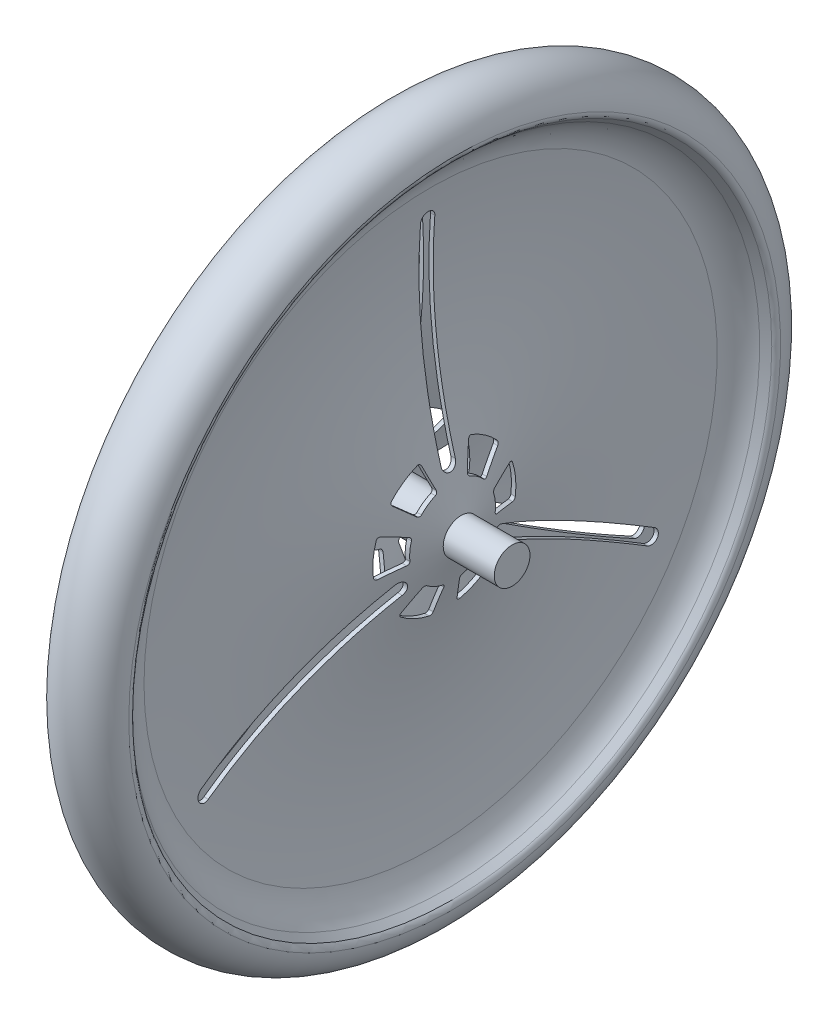
SolidWorks part; units mm, degrees
ref_plane "Front Plane" through (0, 0, 0) normal (0, 0, 1) x (1, 0, 0)
ref_plane "Top Plane" through (0, 0, 0) normal (0, 1, 0) x (1, 0, 0)
ref_plane "Right Plane" through (0, 0, 0) normal (1, 0, 0) x (0, 0, -1)
sketch "Sketch1" plane through (0, 0, 0) normal (0, 0, 1) x (1, 0, 0)
  line L0 (0, 0) -> (351.6274, 0) construction
  line L1 (0, 0) -> (0, 280.0063) construction
  line L2 (23.0895, 223.3969) -> (18.4882, 219.536)
  line L5 (-23.0895, 223.3969) -> (-18.4882, 219.536)
  line L6 (-29.3537, 12.5) -> (29.3537, 12.5)
  arc A0 (-24.8445, 227.784) -> (24.8445, 227.784) centre (0, 225) cw
  arc A1 (8.0072, 200.3052) -> (29.3537, 12.5) centre (404.869, 150.2979) ccw
  arc A2 (18.4882, 219.536) -> (8.0072, 200.3052) centre (37.7718, 196.5546) ccw
  arc A3 (24.8445, 227.784) -> (23.0895, 223.3969) centre (19.8756, 227.2272) cw
  arc A4 (-8.0072, 200.3052) -> (-29.3537, 12.5) centre (-404.869, 150.2979) cw
  arc A5 (-18.4882, 219.536) -> (-8.0072, 200.3052) centre (-37.7718, 196.5546) cw
  arc A6 (-24.8445, 227.784) -> (-23.0895, 223.3969) centre (-19.8756, 227.2272) ccw
  point P2 (0, 250)
  point P27 (9.6791, 212.1442)
  point P31 (25, 225)
  dimension "D2" = 25
  dimension "D6" = 400
  dimension "D7" = 30
  dimension "D8" = 5
  dimension "D1" = 25
  dimension "D3" = 250
  dimension "D4" = 50
  dimension "D5" = 20
revolve "Revolve1" add sketch "Sketch1" angle 360 about L0
shell "Shell2" thickness 3
sketch "Sketch2" plane through (0, 0, 0) normal (1, 0, 0) x (0, 0, -1)
  line L0 (0, 40) -> (0, 180) construction
  line L1 (-5, 40) -> (-5, 180)
  line L2 (5, 40) -> (5, 180)
  line L3 (32.141, -24.3301) -> (153.3846, -94.3301)
  line L4 (37.141, -15.6699) -> (158.3846, -85.6699)
  line L5 (34.641, -20) -> (155.8846, -90) construction
  line L6 (-37.141, -15.6699) -> (-158.3846, -85.6699)
  line L7 (-32.141, -24.3301) -> (-153.3846, -94.3301)
  line L8 (-34.641, -20) -> (-155.8846, -90) construction
  line L9 (10.9232, 30.0114) -> (16.4027, 45.0661)
  line L10 (24.4655, 20.529) -> (36.7382, 30.827)
  line L11 (31.4522, -5.5459) -> (47.2297, -8.3279)
  line L12 (30.0114, 10.9232) -> (45.0661, 16.4027)
  line L13 (5.5459, -31.4522) -> (8.3279, -47.2297)
  line L14 (20.529, -24.4655) -> (30.827, -36.7382)
  line L15 (-20.529, -24.4655) -> (-30.827, -36.7382)
  line L16 (-5.5459, -31.4522) -> (-8.3279, -47.2297)
  line L17 (-30.0114, 10.9232) -> (-45.0661, 16.4027)
  line L18 (-31.4522, -5.5459) -> (-47.2297, -8.3279)
  line L19 (-10.9232, 30.0114) -> (-16.4027, 45.0661)
  line L20 (-24.4655, 20.529) -> (-36.7382, 30.827)
  arc A0 (-5, 40) -> (5, 40) centre (0, 40) ccw
  arc A1 (5, 180) -> (-5, 180) centre (0, 180) ccw
  arc A2 (37.141, -15.6699) -> (32.141, -24.3301) centre (34.641, -20) ccw
  arc A3 (153.3846, -94.3301) -> (158.3846, -85.6699) centre (155.8846, -90) ccw
  arc A4 (-32.141, -24.3301) -> (-37.141, -15.6699) centre (-34.641, -20) ccw
  arc A5 (-158.3846, -85.6699) -> (-153.3846, -94.3301) centre (-155.8846, -90) ccw
  arc A6 (12.0025, 27.4944) -> (21.7312, 20.6823) centre (0, 0) cw
  arc A7 (19.0438, 46.2313) -> (36.9298, 33.7074) centre (0, 0) cw
  arc A8 (12.0025, 27.4944) -> (10.9232, 30.0114) centre (12.8026, 29.3273) cw
  arc A9 (21.7312, 20.6823) -> (24.4655, 20.529) centre (23.1799, 22.0611) ccw
  arc A10 (36.9298, 33.7074) -> (36.7382, 30.827) centre (35.4526, 32.3591) cw
  arc A11 (19.0438, 46.2313) -> (16.4027, 45.0661) centre (18.2821, 44.382) ccw
  arc A12 (49.5594, -6.6232) -> (47.2297, -8.3279) centre (47.577, -6.3583) cw
  arc A13 (29.8121, -3.3527) -> (31.4522, -5.5459) centre (31.7995, -3.5763) ccw
  arc A14 (47.6564, 15.1285) -> (49.5594, -6.6232) centre (0, 0) cw
  arc A15 (47.6564, 15.1285) -> (45.0661, 16.4027) centre (45.7501, 14.5233) ccw
  arc A16 (28.777, 8.4786) -> (30.0114, 10.9232) centre (30.6954, 9.0439) cw
  arc A17 (28.777, 8.4786) -> (29.8121, -3.3527) centre (0, 0) cw
  arc A18 (10.7266, -48.8359) -> (8.3279, -47.2297) centre (10.2975, -46.8824) cw
  arc A19 (7.0458, -29.1609) -> (5.5459, -31.4522) centre (7.5155, -31.1049) ccw
  arc A20 (30.5155, -39.6081) -> (10.7266, -48.8359) centre (0, 0) cw
  arc A21 (30.5155, -39.6081) -> (30.827, -36.7382) centre (29.2949, -38.0238) ccw
  arc A22 (17.8096, -24.1416) -> (20.529, -24.4655) centre (18.9969, -25.7511) cw
  arc A23 (17.8096, -24.1416) -> (7.0458, -29.1609) centre (0, 0) cw
  arc A24 (-30.5155, -39.6081) -> (-30.827, -36.7382) centre (-29.2949, -38.0238) cw
  arc A25 (-10.7266, -48.8359) -> (-30.5155, -39.6081) centre (0, 0) cw
  arc A26 (-10.7266, -48.8359) -> (-8.3279, -47.2297) centre (-10.2975, -46.8824) ccw
  arc A27 (-7.0458, -29.1609) -> (-5.5459, -31.4522) centre (-7.5155, -31.1049) cw
  arc A28 (-7.0458, -29.1609) -> (-17.8096, -24.1416) centre (0, 0) cw
  arc A29 (-17.8096, -24.1416) -> (-20.529, -24.4655) centre (-18.9969, -25.7511) ccw
  arc A30 (-47.6564, 15.1285) -> (-45.0661, 16.4027) centre (-45.7501, 14.5233) cw
  arc A31 (-28.777, 8.4786) -> (-30.0114, 10.9232) centre (-30.6954, 9.0439) ccw
  arc A32 (-49.5594, -6.6232) -> (-47.6564, 15.1285) centre (0, 0) cw
  arc A33 (-49.5594, -6.6232) -> (-47.2297, -8.3279) centre (-47.577, -6.3583) ccw
  arc A34 (-29.8121, -3.3527) -> (-31.4522, -5.5459) centre (-31.7995, -3.5763) cw
  arc A35 (-29.8121, -3.3527) -> (-28.777, 8.4786) centre (0, 0) cw
  arc A36 (-19.0438, 46.2313) -> (-16.4027, 45.0661) centre (-18.2821, 44.382) cw
  arc A37 (-36.9298, 33.7074) -> (-19.0438, 46.2313) centre (0, 0) cw
  arc A38 (-36.9298, 33.7074) -> (-36.7382, 30.827) centre (-35.4526, 32.3591) ccw
  arc A39 (-21.7312, 20.6823) -> (-24.4655, 20.529) centre (-23.1799, 22.0611) cw
  arc A40 (-21.7312, 20.6823) -> (-12.0025, 27.4944) centre (0, 0) cw
  arc A41 (-12.0025, 27.4944) -> (-10.9232, 30.0114) centre (-12.8026, 29.3273) ccw
  point P2 (0, 110)
  point P13 (95.2628, -55)
  point P20 (-95.2628, -55)
  point P25 (0, 0)
  point P51 (0, 0)
  point P100 (0, 0)
  dimension "D5" = 30
  dimension "D6" = 50
  dimension "D9" = 2
  dimension "D1" = 40
  dimension "D2" = 180
  dimension "D3" = 10
  dimension "D7" = 30
  dimension "D8" = 20
  dimension "D11" = 20
  dimension "D4" = 3
  dimension "D10" = 2
extrude "Cut-Extrude1" cut sketch "Sketch2" along normal up to surface and the other way up to surface up to face at (8.0072, 0, 200.3052) other way up to face at (-29.3537, 0, 12.5)
sketch "Sketch3" plane through (0, 0, 0) normal (1, 0, 0) x (0, 0, -1)
  circle A0 centre (0, 0) radius 12.5
  circle A1 centre (0, 0) radius 12.5 construction
extrude "Boss-Extrude1" add sketch "Sketch3" along normal mid plane 130
